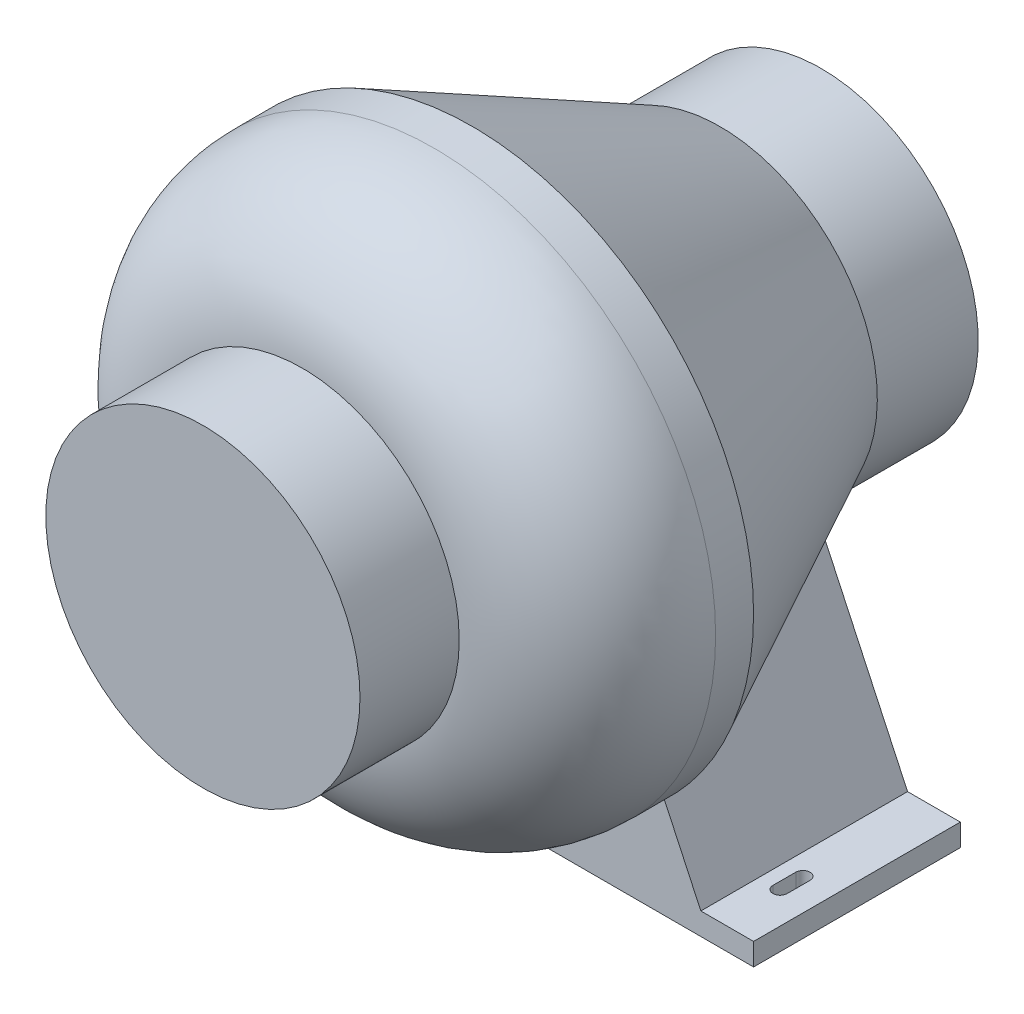
SolidWorks part; units mm, degrees
ref_plane "Front Plane" through (0, 0, 0) normal (0, 0, 1) x (1, 0, 0)
ref_plane "Top Plane" through (0, 0, 0) normal (0, 1, 0) x (1, 0, 0)
ref_plane "Right Plane" through (0, 0, 0) normal (1, 0, 0) x (0, 0, -1)
sketch "Sketch1" plane through (0, 0, 0) normal (0, 0, 1) x (1, 0, 0)
  circle A0 centre (0, 0) radius 47.5
  dimension "D1" = 95
extrude "Boss-Extrude1" add sketch "Sketch1" along normal blind 30.5
sketch "Sketch2" plane through (0, 0, 30.5) normal (0, 0, 1) x (1, 0, 0)
  circle A0 centre (0, 0) radius 85.09
  dimension "D1" = 170.18
extrude "Boss-Extrude2" add sketch "Sketch2" along normal blind 126.4
sketch "Sketch3" plane through (0, 0, 156.9) normal (0, 0, 1) x (1, 0, 0)
  circle A0 centre (0, 0) radius 47.5
  dimension "D1" = 95
extrude "Boss-Extrude3" add sketch "Sketch3" along normal blind 30
sketch "Sketch4" plane through (0, 0, 0) normal (1, 0, 0) x (0, 0, -1)
  line L0 (-30.5, 47.5) -> (-105.5, 85.09)
  line L1 (-30.5, 85.09) -> (-156.9, 85.09) construction
  line L4 (-105.5, 85.09) -> (-30.5, 85.09)
  line L5 (-30.5, -85.09) -> (-30.5, 85.09) construction
  line L6 (-30.5, 85.09) -> (-30.5, 47.5)
  dimension "D1" = 75
ref_axis "Axis1" through (0, 0, 156.9) along (0, 0, -1)
revolve "Cut-Revolve1" cut sketch "Sketch4" angle 360 about axis through (0, 0, 156.9) along (0, 0, -1)
fillet "Fillet1" radius 40 1 edges at (85.09, 0, 156.9)
ref_plane "Plane1" through (0, -92.5, 0) normal (0, 1, 0) x (1, 0, 0)
sketch "Sketch5" plane through (0, -92.5, 0) normal (0, 1, 0) x (1, 0, 0)
  line L0 (85.09, -105.5) -> (-85.09, -105.5) construction
  line L1 (-85.09, -105.5) -> (85.09, -105.5)
  line L2 (-85.09, -105.5) -> (-85.09, -43)
  line L3 (-85.09, -43) -> (85.09, -43)
  line L4 (85.09, -105.5) -> (85.09, -43)
  line L5 (47.5, 0) -> (-47.5, 0) construction
  dimension "D1" = 43
  dimension "D2" = 170.18
  dimension "D3" = 85.09
extrude "Boss-Extrude4" add sketch "Sketch5" along normal up to surface (92.5 mm away) up to plane "Top Plane"
chamfer "Chamfer1" distance 120 angle 25 2 edges at (-85.09, 0, 74.25) (85.09, 0, 74.25) first distance on face at (-85.09, -46.25, 74.25) first distance on face at (85.09, -46.25, 74.25)
sketch "Sketch6" plane through (0, -92.5, 0) normal (0, 1, 0) x (1, 0, 0)
  line L0 (-75.49, -87.9) -> (-75.49, -81) construction
  line L1 (-85.09, -105.5) -> (-67.09, -105.5)
  line L2 (-85.09, -105.5) -> (-85.09, -43)
  line L3 (-85.09, -43) -> (-67.09, -43)
  line L4 (-67.09, -105.5) -> (-67.09, -43)
  line L5 (67.09, -43) -> (85.09, -43)
  line L6 (67.09, -43) -> (67.09, -105.5)
  line L7 (67.09, -105.5) -> (85.09, -105.5)
  line L8 (85.09, -43) -> (85.09, -105.5)
  line L9 (-77.64, -87.9) -> (-77.64, -81)
  line L10 (-73.34, -87.9) -> (-73.34, -81)
  line L11 (47.5, 0) -> (-47.5, 0) construction
  line L12 (75.49, -87.9) -> (75.49, -81) construction
  line L13 (77.64, -87.9) -> (77.64, -81)
  line L14 (0, -43) -> (0, -105.5) construction
  line L15 (43.7231, -43) -> (-43.7231, -43) construction
  line L16 (-72.2665, -105.5) -> (72.2665, -105.5) construction
  line L17 (73.34, -87.9) -> (73.34, -81)
  line L18 (72.2665, -43) -> (-72.2665, -43) construction
  arc A0 (-77.64, -87.9) -> (-73.34, -87.9) centre (-75.49, -87.9) ccw
  arc A1 (-73.34, -81) -> (-77.64, -81) centre (-75.49, -81) ccw
  arc A2 (77.64, -87.9) -> (73.34, -87.9) centre (75.49, -87.9) cw
  arc A3 (73.34, -81) -> (77.64, -81) centre (75.49, -81) cw
  point P14 (-75.49, -84.45)
  point P23 (75.49, -84.45)
  dimension "D1" = 4.3
  dimension "D2" = 6.9
  dimension "D3" = 81
  dimension "D4" = 7.45
  dimension "D5" = 18
  dimension "D6" = 18
extrude "Boss-Extrude5" add sketch "Sketch6" along normal blind 6.7
